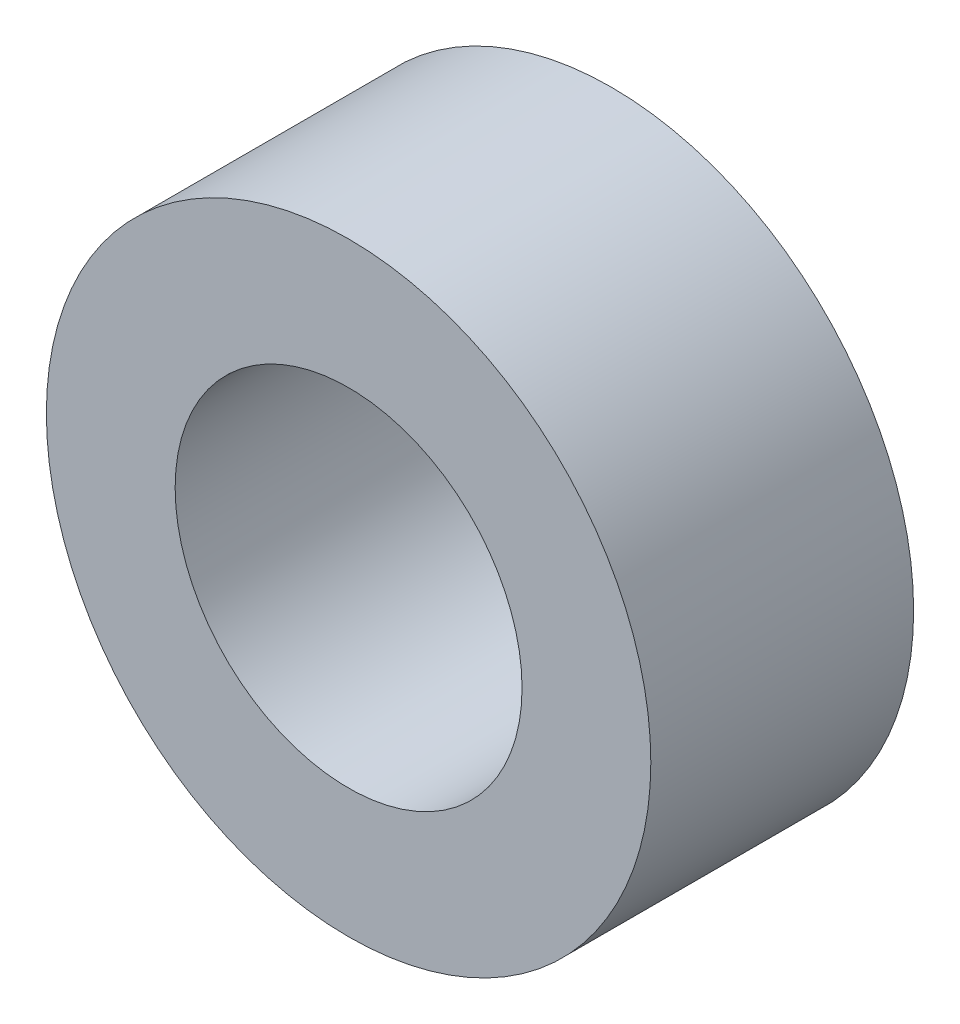
SolidWorks part; units mm, degrees
ref_plane "Front Plane" through (0, 0, 0) normal (0, 0, 1) x (1, 0, 0)
ref_plane "Top Plane" through (0, 0, 0) normal (0, 1, 0) x (1, 0, 0)
ref_plane "Right Plane" through (0, 0, 0) normal (1, 0, 0) x (0, 0, -1)
sketch "Sketch1" plane through (0, 0, 0) normal (0, 0, 1) x (1, 0, 0)
  circle A0 centre (0, 0) radius 2.875
  circle A1 centre (0, 0) radius 1.65
  dimension "D1" = 5.75
  dimension "D2" = 3.3
extrude "Boss-Extrude1" add sketch "Sketch1" along normal blind 2.5
